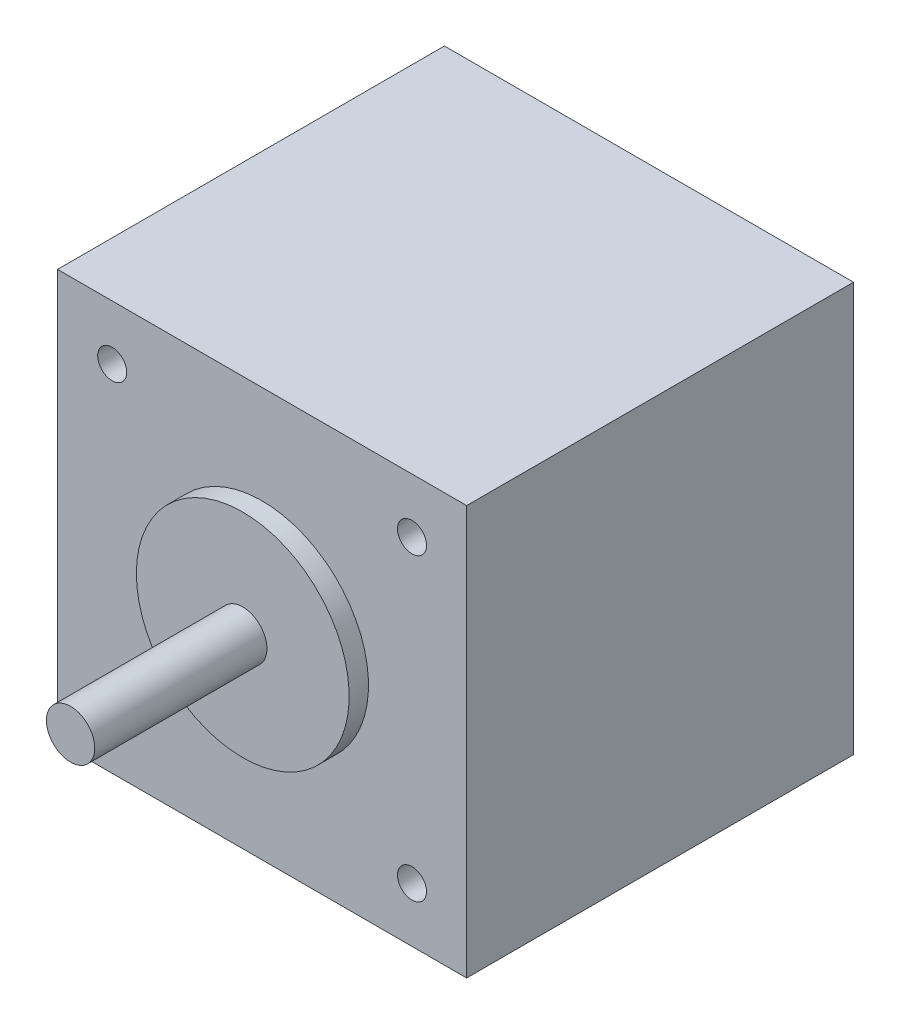
SolidWorks part; units mm, degrees
ref_plane "Спереди" through (0, 0, 0) normal (0, 0, 1) x (1, 0, 0)
ref_plane "Сверху" through (0, 0, 0) normal (0, 1, 0) x (1, 0, 0)
ref_plane "Справа" through (0, 0, 0) normal (1, 0, 0) x (0, 0, -1)
other "Configuration Table"
sketch "Эскиз1" plane through (0, 0, 0) normal (0, 0, 1) x (1, 0, 0)
  line L1 (-21.15, -21.15) -> (21.15, -21.15)
  line L2 (-21.15, -21.15) -> (-21.15, 21.15)
  line L3 (-21.15, 21.15) -> (21.15, 21.15)
  line L4 (21.15, -21.15) -> (21.15, 21.15)
  line L5 (-21.15, -21.15) -> (21.15, 21.15) construction
  line L6 (-21.15, 21.15) -> (21.15, -21.15) construction
  point P0 (0, 0)
  dimension "D1" = 42.3
  dimension "D2" = 42.3
extrude "Корпус" add sketch "Эскиз1" along normal blind 40
sketch "Эскиз2" plane through (0, 0, 0) normal (0, 0, 1) x (1, 0, 0)
  circle A0 centre (0, 0) radius 2.5
extrude "Вал_ПРЕДВ" add sketch "Эскиз2" along normal blind 59.8
sketch "Эскиз3" plane through (0, 0, 0) normal (0, 0, 1) x (1, 0, 0)
  circle A0 centre (0, 0) radius 11
  dimension "D1" = 22
extrude "Буртик_ПРЕДВ" add sketch "Эскиз3" along normal blind 42
sketch "Эскиз4" plane through (0, 0, 0) normal (0, 0, 1) x (1, 0, 0)
  circle A0 centre (0, 0) radius 8
  dimension "D1" = 16
sketch "Эскиз5" plane through (0, 0, 0) normal (0, 0, 1) x (1, 0, 0)
  circle A0 centre (-15.5, -15.5) radius 1.5
  circle A1 centre (-15.5, 15.5) radius 1.5
  circle A2 centre (15.5, -15.5) radius 1.5
  circle A3 centre (15.5, 15.5) radius 1.5
  dimension "D1" = 3
  dimension "D2" = 3
  dimension "D3" = 3
  dimension "D4" = 3
extrude "Крепеж_М3_ПРЕДВ" cut sketch "Эскиз5" against normal blind 4.5 from offset 40
equation "\"Мотор X ширина корпуса\"= 42.3"
equation "\"Мотор X высота корпуса\"= 42.3"
equation "\"Мотор X длина корпуса\"= 40"
equation "\"Мотор X вылет вала\"= 19.8"
equation "\"Мотор Y ширина корпуса\"= 42.3"
equation "\"Мотор Y высота корпуса\"= 42.3"
equation "\"Мотор Y длина корпуса\"= 48"
equation "\"Мотор Y вылет вала\"= 30"
equation "\"Мотор Z ширина корпуса\"= 42"
equation "\"Мотор Z высота корпуса\"= 42"
equation "\"Мотор Z длина корпуса\"= 40"
equation "\"Мотор Z вылет вала\"= 23"
equation "\"Мотор диаметр вала ПРЕДВ\"= 5"
equation "\"Мотор шаг крепления ПРЕДВ\"= 31"
equation "\"Мотор диаметр отверстий ПРЕДВ\"= 3"
equation "\"Мотор глубина отверстий ПРЕДВ\"= 4.5"
equation "\"Мотор диаметр буртика ПРЕДВ\"= 22"
equation "\"Мотор высота буртика ПРЕДВ\"= 2"
equation "\"Мотор диаметр шкива ПРЕДВ\"= 16"
equation "\"Мотор длина шкива ПРЕДВ\"= 12"
equation "\"Мотор отступ шкива ПРЕДВ\"= 5"
equation "\"Мотор X шаг градусов\"= 1.8"
equation "\"Мотор Y шаг градусов\"= 1.8"
equation "\"Мотор Z шаг градусов\"= 1.8"
equation "\"Мотор Y диаметр ротора\"= 25.78"
equation "\"D1@Эскиз1\" = \"Мотор X ширина корпуса\""
equation "\"D1@Корпус\" = \"Мотор X длина корпуса\""
equation "\"D1@Эскиз2\" = \"Мотор диаметр вала ПРЕДВ\""
equation "\"D1@Вал_ПРЕДВ\" = \"Мотор X длина корпуса\" + \"Мотор X вылет вала\""
equation "\"D1@Эскиз3\" = \"Мотор диаметр буртика ПРЕДВ\""
equation "\"D1@Буртик_ПРЕДВ\" = \"Мотор X длина корпуса\" + \"Мотор высота буртика ПРЕДВ\""
equation "\"D1@Эскиз4\" = \"Мотор диаметр шкива ПРЕДВ\""
equation "\"D1@Эскиз5\" = \"Мотор диаметр отверстий ПРЕДВ\""
equation "\"D2@Эскиз5\" = \"Мотор диаметр отверстий ПРЕДВ\""
equation "\"D3@Эскиз5\" = \"Мотор диаметр отверстий ПРЕДВ\""
equation "\"D4@Эскиз5\" = \"Мотор диаметр отверстий ПРЕДВ\""
equation "\"D1@Крепеж_М3_ПРЕДВ\" = \"Мотор глубина отверстий ПРЕДВ\""
equation "\"D19@Крепеж_М3_ПРЕДВ\" = \"Мотор X длина корпуса\""
equation "\"Ширина груза\"= 420"
equation "\"Глубина груза\"= 490"
equation "\"Высота груза\"= 297"
equation "\"Ширина ячейки\"= \"Ширина груза\" + 10"
equation "\"Глубина ячейки\"= \"Глубина груза\" + 10"
equation "\"Высота ячейки\"= \"Высота груза\" + 10 + 13"
equation "\"Колво ячеек ширина\"= 2"
equation "\"Колво ячеек высота\"= 2"
equation "\"Толщина стенки\" = 6"
equation "\"Крепление дверцы\"= 5 "
equation "\"Ширина рейки\"= \"Толщина шестерни\""
equation "\"Высота рейки\"= 20"
equation "\"Высота пола\"= \"Толщина стенки\" * 2"
equation "\"Колво полозьев\"= 5"
equation "\"Отступ рейки\"= 20"
equation "\"Глубина каретки\"= \"Глубина ячейки\" + 30 + \"Мотор Y высота корпуса\" + 20"
equation "\"Отступ шпильки\"= 26"
equation "\"Диаметр шпильки\"= 5"
equation "\"Длинна шпильки\"= ( \"Высота ячейки\" + \"Толщина стенки\" + \"Высота пола\" ) * \"Колво ячеек высота\" + ( \"Толщина стенки\" + \"Отступ рейки\" ) * 2 "
equation "\"Ширина пластины\"= 50  "
equation "\"Высота зона выгрузки\"= \"Высота ячейки\" * 2 + \"Толщина стенки\" * 2"
equation "\"Колво выгрузки\"= 1"
equation "\"Отступ крепления мотора фиксации\" = (\"Ширина пластины\" + 20 - \"Толщина стенки\") / 2"
equation "\"Диаметр оси\"= 10"
equation "\"Диаметр ролика\"= 20"
equation "\"Колво роликов\"= 10"
equation "\"Шаг роликов\"= \"Диаметр ролика\" + 20"
equation "\"Ширина ячейки выгрузки\"= \"Ширина ячейки\" + \"Толщина стенки\" + \"Отступ крепления мотора фиксации\"*2"
equation "\"Длинна рейки\" = (\"Ширина ячейки\" + \"Толщина стенки\" + \"Крепление дверцы\") * \"Колво ячеек ширина\" + \"Ширина ячейки выгрузки\" * \"Колво выгрузки\" + \"Толщина стенки\" + \"Отступ крепления мотора фиксации\" * 2 - \"Крепление дверцы\" * \"Колво ячеек ширина\""
equation "\"Толщина шестерни\"= 10"
